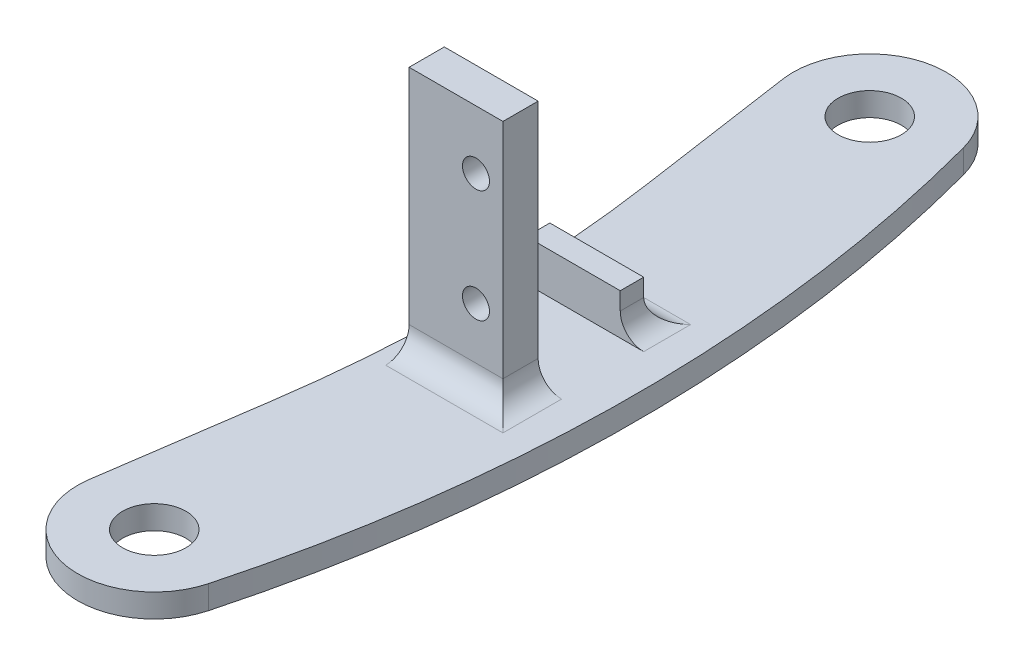
SolidWorks part; units mm, degrees
ref_plane "Front Plane" through (0, 0, 0) normal (0, 0, 1) x (1, 0, 0)
ref_plane "Top Plane" through (0, 0, 0) normal (0, 1, 0) x (1, 0, 0)
ref_plane "Right Plane" through (0, 0, 0) normal (1, 0, 0) x (0, 0, -1)
sketch "Sketch1" plane through (0, 0, 0) normal (0, 0, 1) x (1, 0, 0)
  line L0 (1, 3) -> (11, 3) construction
  line L1 (11, 23) -> (3, 23)
  line L2 (11, 23) -> (11, 2)
  line L3 (11, 2) -> (3, 2)
  line L4 (3, 23) -> (3, 2)
  line L5 (11, 5.5) -> (3, 5.5)
  circle A0 centre (8.7, 18) radius 1.15
  circle A1 centre (8.7, 8.4) radius 1.15
  dimension "D1" = 1
  dimension "D2" = 3.5
  dimension "D3" = 8
extrude "Boss-Extrude1" add sketch "Sketch1" along normal blind 3 contours L5 L2 L1 L4 A1 A0 | L2 L5 L4 L3 region at (6.8927, 14.3163, 0) region at (7, 3.75, 0)
sketch "Sketch2" plane through (0, 0, 0) normal (0, 1, 0) x (1, 0, 0)
  line L0 (0.7878, -12.4454) -> (-1.197, -26.0524)
  line L1 (15.8135, 3.5055) -> (-4.8175, 3.5055) construction
  line L2 (0.7878, 19.4564) -> (-1.197, 33.0634)
  arc A0 (11.5755, -28.6858) -> (11.5755, 35.6967) centre (-108.5639, 3.5055) ccw
  arc A1 (0.7878, -12.4454) -> (0.7878, 19.4564) centre (-108.5639, 3.5055) ccw
  arc A2 (-1.197, -26.0524) -> (11.5755, -28.6858) centre (5.2663, -26.9952) ccw
  arc A4 (-28.4306, -72.5923) -> (-2.6169, -27.9184) centre (-108.5639, 3.5055) ccw construction
  arc A5 (-1.197, 33.0634) -> (11.5755, 35.6967) centre (5.2663, 34.0062) cw
  circle A6 centre (5.2663, 34.0062) radius 2.7
  circle A7 centre (5.2663, -26.9952) radius 2.7
extrude "Boss-Extrude2" add sketch "Sketch2" along normal up to surface (2 mm away) up to face at (7, 2, 1.5)
extrude "Boss-Extrude3" add sketch "Sketch1<3>" against normal blind 2 from offset 7 contours L2 L5 L4 L3 region at (7, 3.75, 0) offset against normal yes
sketch "Sketch1<3>" plane through (0, 0, 0) normal (0, 0, 1) x (1, 0, 0) same geometry as "Sketch1"
fillet "Fillet1" radius 2 4 edges at (7, 2, -9) (11, 2, -8) (11, 2, 1.5) (7, 2, 3)
